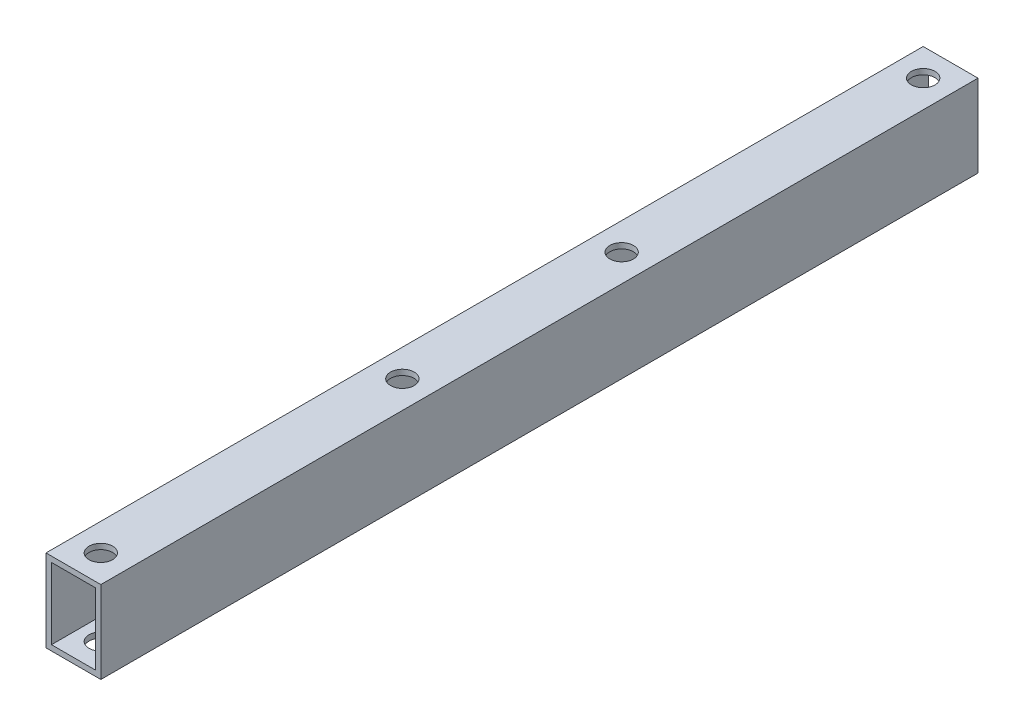
SolidWorks part; units mm, degrees
material "5052-H34"
ref_plane "正面" through (0, 0, 0) normal (0, 0, 1) x (1, 0, 0)
ref_plane "平面" through (0, 0, 0) normal (0, 1, 0) x (1, 0, 0)
ref_plane "右側面" through (0, 0, 0) normal (1, 0, 0) x (0, 0, -1)
sketch "ｽｹｯﾁ1" plane through (0, 0, 0) normal (0, 0, 1) x (1, 0, 0)
  line L1 (-5, 7.5) -> (5, 7.5)
  line L2 (-5, 7.5) -> (-5, -7.5)
  line L3 (-5, -7.5) -> (5, -7.5)
  line L4 (5, 7.5) -> (5, -7.5)
  line L5 (-5, 7.5) -> (5, -7.5) construction
  line L6 (-5, -7.5) -> (5, 7.5) construction
  point P0 (0, 0)
  dimension "D1" = 10
  dimension "D2" = 15
extrude "押し出し-薄板1" add sketch "ｽｹｯﾁ1" along normal blind 160 thin thin type one direction reverse wall 1
sketch "ｽｹｯﾁ2" plane through (0, 7.5, 0) normal (0, 1, 0) x (1, 0, 0)
  line L0 (-5, -80) -> (5, -80) construction
  line L1 (-5, -160) -> (-5, 0) construction
  line L2 (5, -160) -> (5, 0) construction
  line L3 (0, -80) -> (0, -5) construction
  circle A1 centre (0, -60) radius 2.15
  circle A3 centre (0, -100) radius 2.15
  circle A4 centre (0, -5) radius 2.15
  circle A5 centre (0, -155) radius 2.15
  circle A6 centre (0, -155) radius 4 construction
  dimension "D3" = 4.3
  dimension "D5" = 8
  dimension "D1" = 40
  dimension "D4" = 150
extrude "ｶｯﾄ - 押し出し1" cut sketch "ｽｹｯﾁ2" against normal through all
